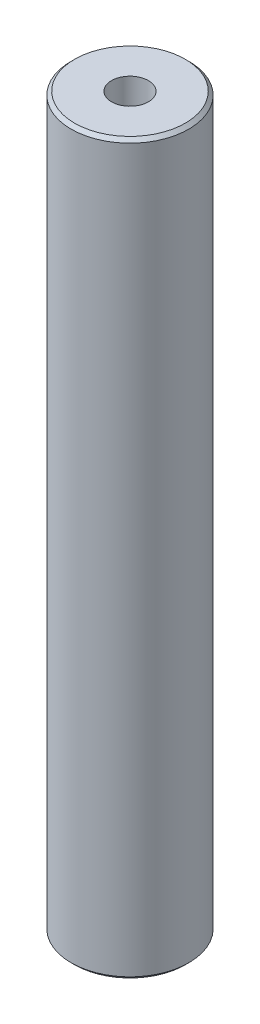
SolidWorks part; units mm, degrees
ref_plane "Front Plane" through (0, 0, 0) normal (0, 0, 1) x (1, 0, 0)
ref_plane "Top Plane" through (0, 0, 0) normal (0, 1, 0) x (1, 0, 0)
ref_plane "Right Plane" through (0, 0, 0) normal (1, 0, 0) x (0, 0, -1)
sketch "Sketch1" plane through (0, 0, 0) normal (0, 1, 0) x (1, 0, 0)
  circle A0 centre (0, 0) radius 35
  dimension "SHAFT_OD" = 70
extrude "Boss-Extrude1" add sketch "Sketch1" along normal blind 433.6547
sketch "Sketch2" plane through (0, 0, 0) normal (0, 1, 0) x (1, 0, 0)
  circle A0 centre (0, 0) radius 10.9717
  dimension "BORE_D" = 21.9435
extrude "Cut-Extrude1" cut sketch "Sketch2" along normal through all
chamfer "Chamfer1" distance 2.052 angle 45 2 edges at (0, 433.6547, 35) (0, 0, 35)
